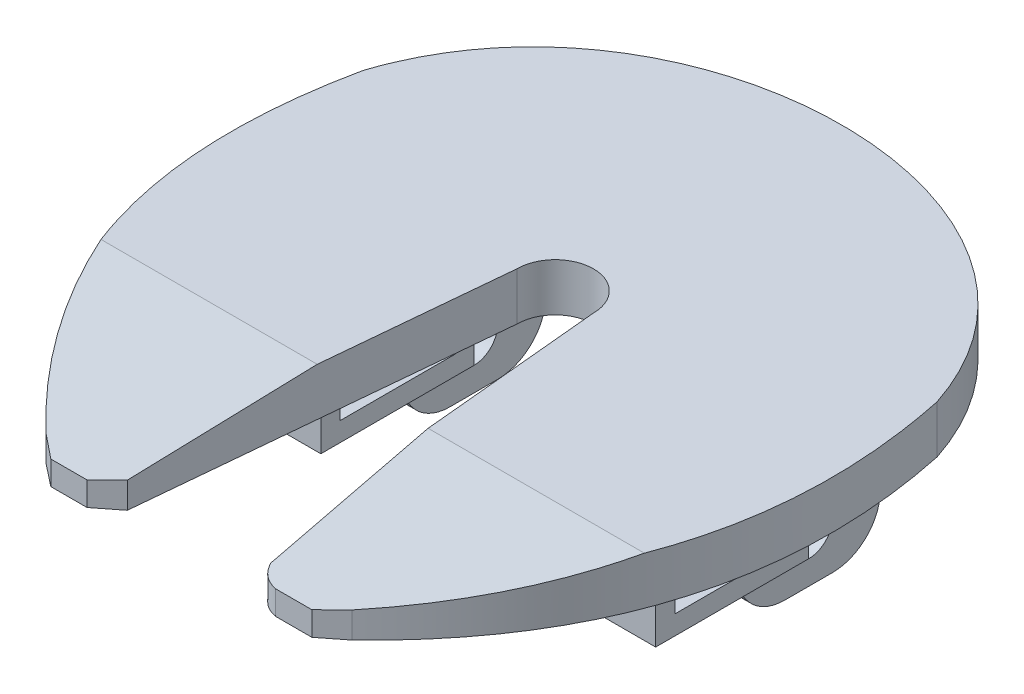
SolidWorks part; units mm, degrees
ref_plane "Front Plane" through (0, 0, 0) normal (0, 0, 1) x (1, 0, 0)
ref_plane "Top Plane" through (0, 0, 0) normal (0, 1, 0) x (1, 0, 0)
ref_plane "Right Plane" through (0, 0, 0) normal (1, 0, 0) x (0, 0, -1)
sketch "Sketch1" plane through (0, 0, 0) normal (0, 1, 0) x (1, 0, 0)
  line L0 (0, 0) -> (60, 0) construction
  line L1 (30, 0) -> (30, -55.8961) construction
  line L2 (26, -9.9147) -> (22.5, -47.1464)
  line L3 (34, -9.9147) -> (37.5, -47.1464)
  line L4 (14, -47.1464) -> (16.3589, -49)
  line L5 (16.3589, -49) -> (20.1411, -49)
  line L6 (20.1411, -49) -> (22.5, -47.1464)
  line L8 (39.8589, -49) -> (43.6411, -49)
  line L9 (43.6411, -49) -> (46, -47.1464)
  line L10 (26, -9.9147) -> (50026, -9.9147) construction
  arc A0 (34, -9.9147) -> (26, -9.9147) centre (30, -9.9147) ccw
  spline S0 degree 3 poles (0, 0) (8.75, 26.7804) (51.25, 26.7804) (60, 0) knots 0 0 0 0 1 1 1 1
  spline S1 degree 2 poles (0, 0) (-5.9385, -28.1192) (14, -47.1464) knots 0 0 0 1 1 1
  spline S2 degree 2 poles (60, 0) (65.9385, -28.1192) (46, -47.1464) knots 0 0 0 1 1 1
  spline S3 degree 2 poles (37.5, -47.1464) (38.1969, -48.6873) (39.8589, -49) knots 0 0 0 1 1 1
  point P11 (30, 0)
  point P12 (30, 20.0853)
  dimension "D13" = 8
  dimension "D1" = 25
  dimension "D2" = 60
  dimension "D3" = 25
  dimension "D4" = 25
  dimension "D5" = 30
  dimension "D6" = 30
  dimension "D7" = 21
  dimension "D8" = 21
  dimension "D9" = 65
  dimension "D10" = 16
  dimension "D11" = 16
  dimension "D12" = 30
  dimension "D14" = 3
  dimension "D15" = 3
  dimension "D16" = 3
  dimension "D17" = 3
  dimension "D18" = 7.5
  dimension "D19" = 7.5
  dimension "D20" = 1.55
  dimension "D21" = 1.55
  dimension "D22" = 49
extrude "Boss-Extrude1" add sketch "Sketch1" along normal blind 5
sketch "Sketch2" plane through (0, 0, 0) normal (0, -1, 0) x (1, 0, 0)
  line L0 (30, 5.9147) -> (30, 12.9147) construction
  line L1 (30, 12.9147) -> (-49970, 12.9147) construction
  line L2 (30, 24.9147) -> (17.9181, 24.9147) construction
  line L3 (57.5, 12.9147) -> (37.5, 12.9147)
  line L4 (57.5, 24.9147) -> (37.5, 24.9147)
  line L5 (22.5, 12.9147) -> (2.5, 12.9147)
  line L6 (22.5, 24.9147) -> (2.5, 24.9147)
  line L7 (57.5, 10.9147) -> (37.5, 10.9147)
  line L8 (22.5, 10.9147) -> (2.5, 10.9147)
  line L9 (57.5, 26.9147) -> (37.5, 26.9147)
  line L10 (22.5, 26.9147) -> (2.5, 26.9147)
  line L11 (57.5, 10.9147) -> (57.5, 12.9147)
  line L12 (37.5, 10.9147) -> (37.5, 12.9147)
  line L13 (2.5, 10.9147) -> (2.5, 12.9147)
  line L14 (22.5, 10.9147) -> (22.5, 12.9147)
  line L15 (2.5, 24.9147) -> (2.5, 26.9147)
  line L16 (22.5, 24.9147) -> (22.5, 26.9147)
  line L17 (37.5, 24.9147) -> (37.5, 26.9147)
  line L18 (57.5, 24.9147) -> (57.5, 26.9147)
  arc A0 (26, 9.9147) -> (34, 9.9147) centre (30, 9.9147) ccw construction
  point P18 (57.5, 27.0589)
  dimension "D1" = 7
  dimension "D2" = 12
  dimension "D3" = 20
  dimension "D4" = 15
  dimension "D5" = 7.5
  dimension "D6" = 2
  dimension "D7" = 2
extrude "Boss-Extrude2" add sketch "Sketch2" along normal blind 3
sketch "Sketch3" plane through (0, -3, 0) normal (0, -1, 0) x (1, 0, 0)
  line L0 (57.5, 10.9147) -> (37.5, 10.9147)
  line L1 (37.5, 10.9147) -> (37.5, 26.9147)
  line L2 (37.5, 26.9147) -> (57.5, 26.9147)
  line L3 (57.5, 26.9147) -> (57.5, 10.9147)
  line L4 (22.5, 10.9147) -> (2.5, 10.9147)
  line L5 (2.5, 10.9147) -> (2.5, 26.9147)
  line L6 (2.5, 26.9147) -> (22.5, 26.9147)
  line L7 (22.5, 26.9147) -> (22.5, 10.9147)
extrude "Boss-Extrude3" add sketch "Sketch3" along normal blind 2
sketch "Sketch5" plane through (0, 0, 0) normal (1, 0, 0) x (0, 0, -1)
  line L0 (-29, 5) -> (-49, 2.5)
  line L1 (0, 5) -> (-47.1464, 5) construction
  line L2 (-49, 5) -> (-49, 0) construction
  line L3 (-49, 2.5) -> (-49, 5)
  line L4 (-49, 5) -> (-29, 5)
  dimension "D1" = 20
extrude "Cut-Extrude1" cut sketch "Sketch5" along normal through all
sketch "Sketch6" plane through (0, 0, 0) normal (0, -1, 0) x (1, 0, 0)
  line L0 (10, 10.9147) -> (10, -4.0853)
  line L1 (10, -4.0853) -> (15, -4.0853)
  line L2 (15, -4.0853) -> (15, 10.9147)
  line L3 (15, 10.9147) -> (10, 10.9147)
  line L4 (2.5, 10.9147) -> (22.5, 10.9147) construction
  point P6 (12.5, 10.9147)
  point P7 (12.5, 10.9147)
  point P8 (10, -7.2474)
  point P9 (10, 7.7097)
  dimension "D1" = 15
  dimension "D2" = 5
extrude "Boss-Extrude4" add sketch "Sketch6" along normal blind 15
ref_plane "Plane1" through (30, 0, 0) normal (1, 0, 0) x (0, 0, -1)
mirror "Mirror1" about plane through (30, 0, 0) normal (1, 0, 0) of "Boss-Extrude4"
sketch "Sketch7" plane through (10, 0, 0) normal (-1, 0, 0) x (0, 0, 1)
  line L0 (0, 0) -> (47.1464, 0) construction
  line L1 (10.9147, -15) -> (-4.0853, -15) construction
  circle A0 centre (3.4147, -10) radius 2.5
  point P2 (0, 0)
  point P5 (0, 0)
  point P8 (3.4147, -15)
  dimension "D1" = 5
  dimension "D2" = 10
extrude "Cut-Extrude2" cut sketch "Sketch7" against normal up to surface (40 mm away) up to face at (50, -7, 4.9147)
fillet "Fillet1" radius 5 4 edges at (12.5, -15, -4.0853) (12.5, -15, 10.9147) (47.5, -15, 10.9147) (47.5, -15, -4.0853)
